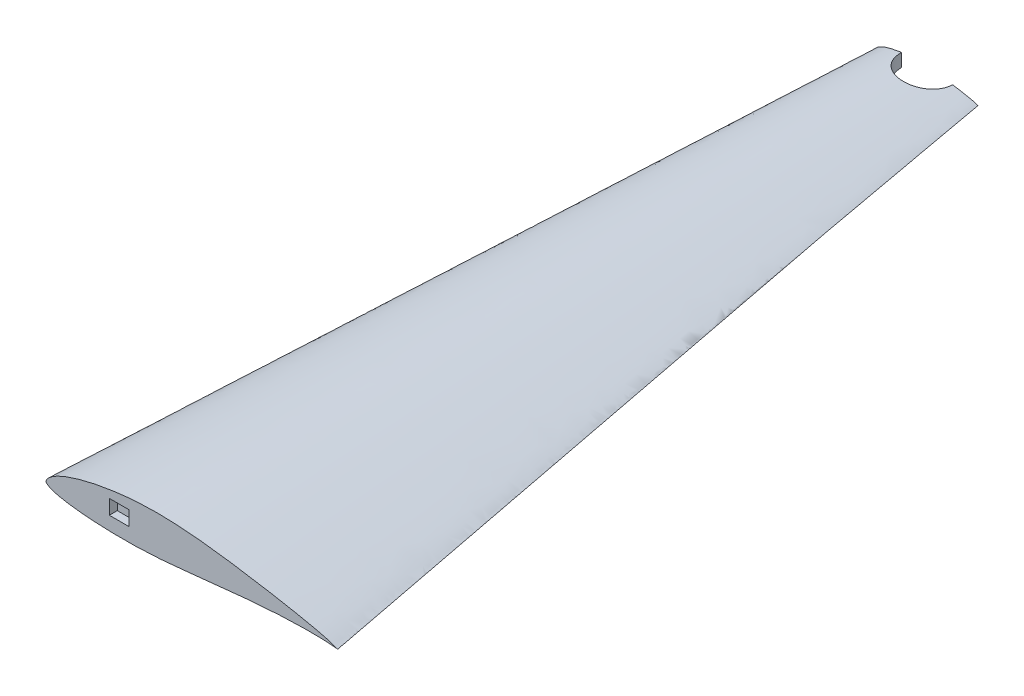
SolidWorks part; units mm, degrees
ref_plane "Front Plane" through (0, 0, 0) normal (0, 0, 1) x (1, 0, 0)
ref_plane "Top Plane" through (0, 0, 0) normal (0, 1, 0) x (1, 0, 0)
ref_plane "Right Plane" through (0, 0, 0) normal (1, 0, 0) x (0, 0, -1)
curve "Curve1"
  spline degree 3 poles (0.9921, 0.0008, 0) (1.0019, -0.0008, 0) (0.9929, 0.0016, 0) (0.9861, 0.0043, 0) (0.9706, 0.0096, 0) (0.9519, 0.0152, 0) (0.9278, 0.021, 0) (0.8992, 0.0273, 0) (0.8662, 0.0341, 0) (0.8293, 0.0413, 0) (0.789, 0.0488, 0) (0.746, 0.0564, 0) (0.7007, 0.0641, 0) (0.6538, 0.0714, 0) (0.6058, 0.0784, 0) (0.5573, 0.0846, 0) (0.5088, 0.0898, 0) (0.4609, 0.0938, 0) (0.4138, 0.0961, 0) (0.3679, 0.0966, 0) (0.3232, 0.0952, 0) (0.2801, 0.092, 0) (0.2388, 0.0874, 0) (0.1997, 0.0815, 0) (0.1631, 0.0746, 0) (0.1296, 0.0669, 0) (0.0993, 0.0585, 0) (0.0726, 0.0496, 0) (0.0499, 0.0404, 0) (0.0312, 0.031, 0) (0.0168, 0.0217, 0) (0.0085, 0.0145, 0) (0.0039, 0.009, 0) (0.0018, 0.0058, 0) (0.0004, 0.0024, 0) (0, 0.0003, 0) (0, -0.0012, 0) (0.0006, -0.0026, 0) (0.002, -0.0043, 0) (0.0049, -0.007, 0) (0.0107, -0.0108, 0) (0.0215, -0.0156, 0) (0.0378, -0.0206, 0) (0.0598, -0.0253, 0) (0.0864, -0.0294, 0) (0.1174, -0.033, 0) (0.1523, -0.036, 0) (0.1908, -0.0383, 0) (0.2323, -0.0397, 0) (0.2764, -0.0402, 0) (0.3228, -0.0395, 0) (0.3711, -0.0373, 0) (0.4212, -0.0335, 0) (0.4729, -0.0284, 0) (0.526, -0.0227, 0) (0.5798, -0.0169, 0) (0.6336, -0.0114, 0) (0.6866, -0.0064, 0) (0.7378, -0.0023, 0) (0.7866, 0.0009, 0) (0.832, 0.0031, 0) (0.8733, 0.0042, 0) (0.9096, 0.0045, 0) (0.9406, 0.0038, 0) (0.9645, 0.0029, 0) (0.984, 0.0013, 0) (0.9921, 0.0008, 0) (1.0019, -0.0008, 0) (0.9929, 0.0016, 0) knots -0.016161 -0.007282 -0.001839 0 0.00178 0.006777 0.014308 0.024046 0.036116 0.050547 0.06713 0.085624 0.105767 0.127282 0.149864 0.17323 0.197069 0.221103 0.245052 0.268663 0.291773 0.314299 0.336178 0.357377 0.377792 0.397225 0.415489 0.432417 0.447849 0.461651 0.473687 0.483898 0.492263 0.498797 0.499955 0.502811 0.504371 0.50536 0.505925 0.506503 0.507535 0.509205 0.512345 0.517665 0.526422 0.537425 0.550643 0.565966 0.583206 0.602155 0.622587 0.644255 0.666998 0.690703 0.715307 0.740824 0.767084 0.793717 0.820331 0.846519 0.871863 0.895937 0.918335 0.938667 0.956573 0.971715 0.983839 0.992718 0.998161 1 1.00178 1.006777 1.014308 periodic
sketch "Sketch1" plane through (0, 0, 0) normal (0, 0, 1) x (1, 0, 0)
  line L0 (1122.2059, -30.8288) -> (-1162.7941, -35.0845) construction
  spline S1 degree 3 poles (1104.1363, -28.0222) (1126.6295, -31.7875) (1105.8826, -26.3024) (1090.4575, -20.1288) (1054.9513, -7.9956) (1012.296, 4.6638) (957.0478, 17.8508) (891.7164, 32.0367) (816.2153, 47.3864) (731.9108, 63.6705) (639.9041, 80.612) (541.5101, 97.9168) (438.0076, 115.0958) (330.7593, 131.7488) (221.0675, 147.3336) (110.2357, 161.251) (-0.493, 172.9975) (-110.0556, 181.8587) (-217.6516, 186.9061) (-322.6724, 187.859) (-424.6755, 184.4831) (-523.1626, 176.9995) (-617.5035, 166.1709) (-706.8843, 152.6667) (-790.3524, 136.737) (-867.0563, 118.889) (-936.2082, 99.5088) (-997.0691, 79.0242) (-1049.0447, 57.9028) (-1091.6336, 36.4479) (-1124.4686, 15.1943) (-1143.3869, -1.4067) (-1153.8659, -14.0298) (-1158.6984, -21.3016) (-1161.9612, -29.0988) (-1162.8988, -33.8887) (-1162.7223, -37.2464) (-1161.3764, -40.4052) (-1158.2301, -44.4654) (-1151.5185, -50.6376) (-1138.2079, -59.2164) (-1113.635, -70.0567) (-1076.2399, -81.3981) (-1026.0446, -92.1031) (-965.2298, -101.4019) (-894.4776, -109.4657) (-814.6314, -116.0953) (-726.7099, -121.1028) (-631.8133, -124.2931) (-530.9633, -125.2112) (-425.0342, -123.2363) (-314.6436, -117.9744) (-200.1569, -109.1265) (-81.9663, -97.1903) (39.2548, -83.9633) (162.1641, -70.4688) (285.0306, -57.6215) (406.0083, -46.0046) (523.1884, -36.2734) (634.6311, -28.7415) (738.3789, -23.5277) (832.7109, -20.7776) (915.5317, -20.0924) (986.36, -21.3847) (1040.9806, -23.338) (1085.6437, -26.9173) (1104.1363, -28.0222) (1126.6295, -31.7875) (1105.8826, -26.3024) knots -0.016161 -0.007282 -0.001839 0 0.00178 0.006777 0.014308 0.024046 0.036116 0.050547 0.06713 0.085624 0.105767 0.127282 0.149864 0.17323 0.197069 0.221103 0.245052 0.268663 0.291773 0.314299 0.336178 0.357377 0.377792 0.397225 0.415489 0.432417 0.447849 0.461651 0.473687 0.483898 0.492263 0.498797 0.499955 0.502811 0.504371 0.50536 0.505925 0.506503 0.507535 0.509205 0.512345 0.517665 0.526422 0.537425 0.550643 0.565966 0.583206 0.602155 0.622587 0.644255 0.666998 0.690703 0.715307 0.740824 0.767084 0.793717 0.820331 0.846519 0.871863 0.895937 0.918335 0.938667 0.956573 0.971715 0.983839 0.992718 0.998161 1 1.00178 1.006777 1.014308 only from (1122.2059, -30.8288) to (1122.2059, -30.8288)
  dimension "D1" = 2285
ref_plane "Plane1" through (0, 0, 6200) normal (0, 0, 1) x (1, 0, 0)
ref_plane "Plane3" through (0, -35.0845, 0) normal (0, 1, 0) x (1, 0, 0)
sketch "Sketch4" plane through (0, -35.0845, 0) normal (0, 1, 0) x (1, 0, 0)
  line L1 (1122.2059, 0) -> (-1162.7941, 0) construction
  line L2 (-172.1886, -6200) -> (172.1886, -6200) construction
  line L4 (-1162.7941, 0) -> (-862.7941, -6200)
sketch "Sketch5" plane through (0, 0, 6200) normal (0, 0, 1) x (1, 0, 0)
  line L0 (-62.749, -35.2354) -> (-862.7688, -35.3009) construction
  spline S1 degree 3 poles (-69.0897, -34.3504) (-61.22, -35.5469) (-68.4893, -33.741) (-73.9048, -31.6671) (-86.3598, -27.6181) (-101.3126, -23.4229) (-120.663, -19.1093) (-143.5377, -14.4998) (-169.9677, -9.5373) (-199.4749, -4.2947) (-231.6736, 1.1372) (-266.1033, 6.6624) (-302.3153, 12.1171) (-339.8318, 17.3686) (-378.1955, 22.2345) (-416.9483, 26.5125) (-455.6538, 30.0335) (-493.9373, 32.5536) (-531.5145, 33.7529) (-568.1715, 33.5367) (-603.7528, 31.8256) (-638.0855, 28.6992) (-670.9538, 24.4271) (-702.0769, 19.2472) (-731.124, 13.2516) (-757.8002, 6.6219) (-781.8329, -0.5031) (-802.9662, -7.9701) (-820.9952, -15.6131) (-835.7466, -23.3233) (-847.0949, -30.9123) (-853.6106, -36.8049) (-857.2018, -41.2651) (-858.8503, -43.8282) (-859.9483, -46.5664) (-860.2505, -48.243) (-860.1714, -49.4139) (-859.6851, -50.5093) (-858.5659, -51.9099) (-856.1913, -54.0289) (-851.5011, -56.9533) (-842.8685, -60.6082) (-829.7584, -64.3709) (-812.1844, -67.8447) (-790.9116, -70.7722) (-766.1771, -73.2167) (-738.2762, -75.1133) (-707.5656, -76.4015) (-674.4302, -77.0191) (-639.2289, -76.8125) (-602.2702, -75.5698) (-563.7715, -73.1566) (-523.8621, -69.4706) (-482.6761, -64.6873) (-440.4393, -59.4377) (-397.6147, -54.086) (-354.8016, -48.9603) (-312.6413, -44.2739) (-271.7964, -40.2655) (-232.9425, -37.0546) (-196.7619, -34.6929) (-163.8546, -33.2402) (-134.9538, -32.5684) (-110.2281, -32.6493) (-91.1554, -33.0456) (-75.5494, -34.0614) (-69.0897, -34.3504) (-61.22, -35.5469) (-68.4893, -33.741) knots -0.016161 -0.007282 -0.001839 0 0.00178 0.006777 0.014308 0.024046 0.036116 0.050547 0.06713 0.085624 0.105767 0.127282 0.149864 0.17323 0.197069 0.221103 0.245052 0.268663 0.291773 0.314299 0.336178 0.357377 0.377792 0.397225 0.415489 0.432417 0.447849 0.461651 0.473687 0.483898 0.492263 0.498797 0.499955 0.502811 0.504371 0.50536 0.505925 0.506503 0.507535 0.509205 0.512345 0.517665 0.526422 0.537425 0.550643 0.565966 0.583206 0.602155 0.622587 0.644255 0.666998 0.690703 0.715307 0.740824 0.767084 0.793717 0.820331 0.846519 0.871863 0.895937 0.918335 0.938667 0.956573 0.971715 0.983839 0.992718 0.998161 1 1.00178 1.006777 1.014308 only from (-62.7688, -35.2354) to (-62.7688, -35.2354)
  dimension "D1" = 800
sketch "Sketch6" plane through (0, 0, 6200) normal (0, 0, 1) x (1, 0, 0)
  line L0 (-862.7688, -35.3009) -> (-860.1517, -49.246)
  spline S0 degree 3 poles (-69.0897, -34.3504) (-61.22, -35.5469) (-68.4893, -33.741) (-73.9048, -31.6671) (-86.3598, -27.6181) (-101.3126, -23.4229) (-120.663, -19.1093) (-143.5377, -14.4998) (-169.9677, -9.5373) (-199.4749, -4.2947) (-231.6736, 1.1372) (-266.1033, 6.6624) (-302.3153, 12.1171) (-339.8318, 17.3686) (-378.1955, 22.2345) (-416.9483, 26.5125) (-455.6538, 30.0335) (-493.9373, 32.5536) (-531.5145, 33.7529) (-568.1715, 33.5367) (-603.7528, 31.8256) (-638.0855, 28.6992) (-670.9538, 24.4271) (-702.0769, 19.2472) (-731.124, 13.2516) (-757.8002, 6.6219) (-781.8329, -0.5031) (-802.9662, -7.9701) (-820.9952, -15.6131) (-835.7466, -23.3233) (-847.0949, -30.9123) (-853.6106, -36.8049) (-857.2018, -41.2651) (-858.8503, -43.8282) (-859.9483, -46.5664) (-860.2505, -48.243) (-860.1714, -49.4139) (-859.6851, -50.5093) (-858.5659, -51.9099) (-856.1913, -54.0289) (-851.5011, -56.9533) (-842.8685, -60.6082) (-829.7584, -64.3709) (-812.1844, -67.8447) (-790.9116, -70.7722) (-766.1771, -73.2167) (-738.2762, -75.1133) (-707.5656, -76.4015) (-674.4302, -77.0191) (-639.2289, -76.8125) (-602.2702, -75.5698) (-563.7715, -73.1566) (-523.8621, -69.4706) (-482.6761, -64.6873) (-440.4393, -59.4377) (-397.6147, -54.086) (-354.8016, -48.9603) (-312.6413, -44.2739) (-271.7964, -40.2655) (-232.9425, -37.0546) (-196.7619, -34.6929) (-163.8546, -33.2402) (-134.9538, -32.5684) (-110.2281, -32.6493) (-91.1554, -33.0456) (-75.5494, -34.0614) (-69.0897, -34.3504) (-61.22, -35.5469) (-68.4893, -33.741) knots -0.016161 -0.007282 -0.001839 0 0.00178 0.006777 0.014308 0.024046 0.036116 0.050547 0.06713 0.085624 0.105767 0.127282 0.149864 0.17323 0.197069 0.221103 0.245052 0.268663 0.291773 0.314299 0.336178 0.357377 0.377792 0.397225 0.415489 0.432417 0.447849 0.461651 0.473687 0.483898 0.492263 0.498797 0.499955 0.502811 0.504371 0.50536 0.505925 0.506503 0.507535 0.509205 0.512345 0.517665 0.526422 0.537425 0.550643 0.565966 0.583206 0.602155 0.622587 0.644255 0.666998 0.690703 0.715307 0.740824 0.767084 0.793717 0.820331 0.846519 0.871863 0.895937 0.918335 0.938667 0.956573 0.971715 0.983839 0.992718 0.998161 1 1.00178 1.006777 1.014308 only from (-62.7688, -35.2354) to (-62.7688, -35.2354) construction
ref_axis "Axis2" through (-860.1517, -49.246, 6200) along (-0.0488, 0.0023, -0.9988)
loft "Loft5" add profiles "Sketch1", "Sketch5" connector at (-829.2128, 127.5517, 0) connector at (-729.5824, 13.4038, 6200)
sketch "Sketch9" plane through (0, 0, 0) normal (0, 0, -1) x (-1, 0, 0)
  line L1 (513.5943, 97.9459) -> (666.6195, 97.9459)
  line L2 (513.5943, 97.9459) -> (513.5943, -16.278)
  line L3 (513.5943, -16.278) -> (666.6195, -16.278)
  line L4 (666.6195, 97.9459) -> (666.6195, -16.278)
  line L5 (513.5943, 97.9459) -> (666.6195, -16.278) construction
  line L6 (513.5943, -16.278) -> (666.6195, 97.9459) construction
  point P0 (590.1069, 40.8339)
extrude "Boss-Extrude1" add sketch "Sketch9" along normal blind 30
mirror "Mirror3" about plane through (0, 0, -30) normal (0, 0, -1) of bodies 104
sketch "Sketch10" plane through (0, 0, 6200) normal (0, 0, 1) x (1, 0, 0)
  line L1 (1321.2817, -875.42) -> (-2414.7647, -875.42)
  line L2 (1321.2817, -875.42) -> (1321.2817, 875.42)
  line L3 (1321.2817, 875.42) -> (-2414.7647, 875.42)
  line L4 (-2414.7647, -875.42) -> (-2414.7647, 875.42)
  line L5 (1321.2817, -875.42) -> (-2414.7647, 875.42) construction
  line L6 (1321.2817, 875.42) -> (-2414.7647, -875.42) construction
  point P0 (-546.7415, 0)
extrude "Cut-Extrude1" cut sketch "Sketch10" against normal blind 6202
sketch "Sketch12" plane through (0, 0, -2) normal (0, 0, 1) x (1, 0, 0)
  line L4 (-666.6195, 97.9459) -> (-666.6195, -16.278)
  line L5 (-666.6195, -16.278) -> (-513.5943, -16.278)
  line L6 (-513.5943, -16.278) -> (-513.5943, 97.9459)
  line L7 (-513.5943, 97.9459) -> (-666.6195, 97.9459)
  line L8 (-666.6195, 97.9459) -> (-666.6195, -16.278)
  line L9 (-666.6195, -16.278) -> (-513.5943, -16.278)
  line L10 (-513.5943, -16.278) -> (-513.5943, 97.9459)
  line L11 (-513.5943, 97.9459) -> (-666.6195, 97.9459)
  dimension "D1" = 0
extrude "Cut-Extrude2" cut sketch "Sketch12" against normal blind 120
extrude "Cut-Extrude3" cut sketch "Sketch13" along normal blind 17000
sketch "Sketch13" plane through (-2172.4747, -6356.5137, -7432.8161) normal (0, 1, 0) x (1, 0, 0)
  circle A0 centre (1710.9861, -1172.8161) radius 200
